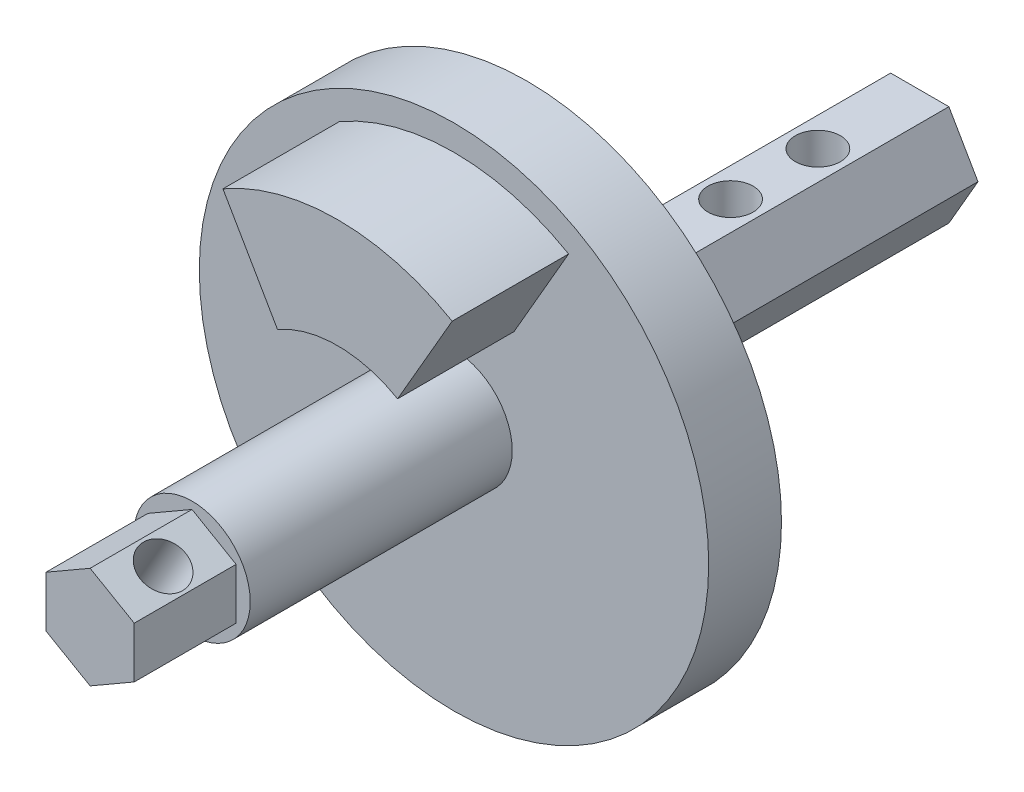
SolidWorks part; units mm, degrees
ref_plane "Front Plane" through (0, 0, 0) normal (0, 0, 1) x (1, 0, 0)
ref_plane "Top Plane" through (0, 0, 0) normal (0, 1, 0) x (1, 0, 0)
ref_plane "Right Plane" through (0, 0, 0) normal (1, 0, 0) x (0, 0, -1)
sketch "Sketch1" plane through (0, 0, 0) normal (0, 0, 1) x (1, 0, 0)
  circle A0 centre (0, 0) radius 17.5
  dimension "D1" = 35
extrude "Boss-Extrude1" add sketch "Sketch1" along normal mid plane 5
sketch "Sketch2" plane through (0, 0, 2.5) normal (0, 0, 1) x (1, 0, 0)
  line L3 (0, 0) -> (0, 11) construction
  line L4 (7.875, 13.6399) -> (4.125, 7.1447)
  line L5 (-4.125, 7.1447) -> (-7.875, 13.6399)
  arc A1 (4.125, 7.1447) -> (-4.125, 7.1447) centre (0, 0) ccw
  arc A6 (-7.875, 13.6399) -> (7.875, 13.6399) centre (0, 0) cw
  circle A7 centre (0, 0) radius 17.5 construction
  dimension "D2" = 7.5
  dimension "D3" = 1.75
  dimension "D1" = 30
extrude "Boss-Extrude2" add sketch "Sketch2" along normal blind 8
sketch "Sketch3" plane through (0, 0, 2.5) normal (0, 0, 1) x (1, 0, 0)
  circle A0 centre (0, 0) radius 4
extrude "Boss-Extrude3" add sketch "Sketch3" along normal blind 18
sketch "Sketch7" plane through (0, 0, -2.5) normal (0, 0, -1) x (-1, 0, 0)
  circle A0 centre (0, 0) radius 4
extrude "Boss-Extrude4" add sketch "Sketch7" along normal blind 7
sketch "Sketch9" plane through (0, 0, -9.5) normal (0, 0, -1) x (-1, 0, 0)
  line L0 (-4, 0) -> (4, 0) construction
  line L1 (2, -3.4641) -> (-2, 3.4641) construction
  line L2 (-2, -3.4641) -> (2, 3.4641) construction
  line L23 (4, 0) -> (2, 3.4641)
  line L24 (2, 3.4641) -> (-2, 3.4641)
  line L25 (-2, 3.4641) -> (-4, 0)
  line L26 (-4, 0) -> (-2, -3.4641)
  line L27 (-2, -3.4641) -> (2, -3.4641)
  line L28 (2, -3.4641) -> (4, 0)
  circle A1 centre (0, 0) radius 4 construction
  point P2 (0, 0)
  point P5 (0, 0)
  point P6 (0, 0)
  point P8 (0, 0)
  point P10 (0, 0)
  point P11 (0, 0)
  point P13 (0, 0)
  point P15 (0, 0)
  point P16 (0, 0)
  point P18 (0, 0)
  point P20 (0, 0)
  point P21 (0, 0)
extrude "Boss-Extrude5" add sketch "Sketch9" along normal blind 20
sketch "Sketch10" plane through (0, -3.4641, 0) normal (0, 1, 0) x (-1, 0, 0)
  circle A0 centre (0, -22.5) radius 1.55
  circle A1 centre (0, -16.5) radius 1.55
  point P11 (0, -29.5)
extrude "Cut-Extrude1" cut sketch "Sketch10" along normal blind 7
sketch "Sketch11" plane through (0, 0, 20.5) normal (0, 0, 1) x (1, 0, 0)
  line L4 (3.0311, 1.75) -> (0, 3.5)
  line L5 (0, 3.5) -> (-3.0311, 1.75)
  line L6 (-3.0311, 1.75) -> (-3.0311, -1.75)
  line L7 (-3.0311, -1.75) -> (0, -3.5)
  line L8 (0, -3.5) -> (3.0311, -1.75)
  line L9 (3.0311, -1.75) -> (3.0311, 1.75)
extrude "Boss-Extrude6" add sketch "Sketch11" along normal blind 7
sketch "Sketch12" plane through (-1.5155, -2.625, 0) normal (-0.5, -0.866, 0) x (0.866, -0.5, 0)
  circle A0 centre (0, 24) radius 1.55
extrude "Cut-Extrude2" cut sketch "Sketch12" against normal blind 6.1
